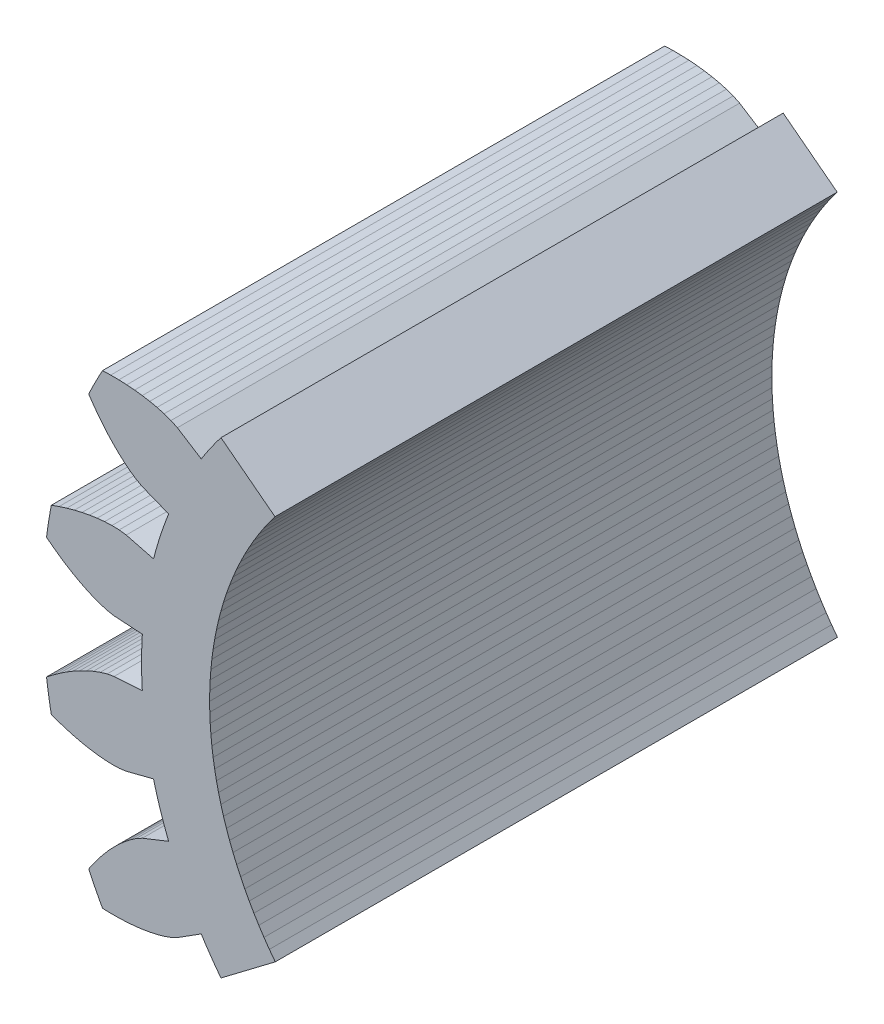
SolidWorks part; units mm, degrees
ref_plane "Alzado" through (0, 0, 0) normal (0, 0, 1) x (1, 0, 0)
ref_plane "Planta" through (0, 0, 0) normal (0, 1, 0) x (1, 0, 0)
ref_plane "Vista lateral" through (0, 0, 0) normal (1, 0, 0) x (0, 0, -1)
sketch "Croquis1" plane through (0, 0, 0) normal (0, 0, 1) x (1, 0, 0)
  line L0 (-17.3546, 13.3167) -> (-17.524, 13.0929)
  line L1 (-17.524, 13.0929) -> (-17.6906, 12.867)
  line L2 (-17.6906, 12.867) -> (-17.8542, 12.6389)
  line L3 (-17.8542, 12.6389) -> (-18.0149, 12.4088)
  line L4 (-18.0149, 12.4088) -> (-18.1726, 12.1767)
  line L5 (-18.1726, 12.1767) -> (-18.3274, 11.9425)
  line L6 (-18.3274, 11.9425) -> (-18.4791, 11.7064)
  line L7 (-18.4791, 11.7064) -> (-18.8185, 11.9214)
  line L8 (-18.8185, 11.9214) -> (-19.1579, 12.1364)
  line L9 (-19.1579, 12.1364) -> (-19.4973, 12.3514)
  line L10 (-19.4973, 12.3514) -> (-19.8367, 12.5664)
  line L11 (-19.8367, 12.5664) -> (-20.2018, 12.7408)
  line L12 (-20.2018, 12.7408) -> (-20.5901, 12.878)
  line L13 (-20.5901, 12.878) -> (-20.9936, 12.9901)
  line L14 (-20.9936, 12.9901) -> (-21.4094, 13.0809)
  line L15 (-21.4094, 13.0809) -> (-21.8359, 13.1525)
  line L16 (-21.8359, 13.1525) -> (-22.272, 13.2059)
  line L17 (-22.272, 13.2059) -> (-22.7168, 13.2422)
  line L18 (-22.7168, 13.2422) -> (-23.1695, 13.2617)
  line L19 (-23.1695, 13.2617) -> (-23.6295, 13.265)
  line L20 (-23.6295, 13.265) -> (-24.0962, 13.2523)
  line L21 (-24.0962, 13.2523) -> (-24.2617, 12.9468)
  line L22 (-24.2617, 12.9468) -> (-24.4233, 12.6393)
  line L23 (-24.4233, 12.6393) -> (-24.5811, 12.3297)
  line L24 (-24.5811, 12.3297) -> (-24.7349, 12.0182)
  line L25 (-24.7349, 12.0182) -> (-24.8847, 11.7047)
  line L26 (-24.8847, 11.7047) -> (-24.6207, 11.3197)
  line L27 (-24.6207, 11.3197) -> (-24.3477, 10.9495)
  line L28 (-24.3477, 10.9495) -> (-24.0657, 10.5947)
  line L29 (-24.0657, 10.5947) -> (-23.775, 10.2562)
  line L30 (-23.775, 10.2562) -> (-23.4754, 9.9348)
  line L31 (-23.4754, 9.9348) -> (-23.1668, 9.6318)
  line L32 (-23.1668, 9.6318) -> (-22.8489, 9.3488)
  line L33 (-22.8489, 9.3488) -> (-22.5211, 9.0883)
  line L34 (-22.5211, 9.0883) -> (-22.1819, 8.8548)
  line L35 (-22.1819, 8.8548) -> (-21.8262, 8.6619)
  line L36 (-21.8262, 8.6619) -> (-21.4527, 8.5137)
  line L37 (-21.4527, 8.5137) -> (-21.0793, 8.3655)
  line L38 (-21.0793, 8.3655) -> (-20.7058, 8.2173)
  line L39 (-20.7058, 8.2173) -> (-20.3324, 8.0691)
  line L40 (-20.3324, 8.0691) -> (-20.4757, 7.6981)
  line L41 (-20.4757, 7.6981) -> (-20.6123, 7.3245)
  line L42 (-20.6123, 7.3245) -> (-20.7421, 6.9486)
  line L43 (-20.7421, 6.9486) -> (-20.865, 6.5703)
  line L44 (-20.865, 6.5703) -> (-20.981, 6.1899)
  line L45 (-20.981, 6.1899) -> (-21.09, 5.8075)
  line L46 (-21.09, 5.8075) -> (-21.1921, 5.4231)
  line L47 (-21.1921, 5.4231) -> (-21.5814, 5.5227)
  line L48 (-21.5814, 5.5227) -> (-21.9706, 5.6223)
  line L49 (-21.9706, 5.6223) -> (-22.3599, 5.7219)
  line L50 (-22.3599, 5.7219) -> (-22.7491, 5.8215)
  line L51 (-22.7491, 5.8215) -> (-23.1502, 5.8745)
  line L52 (-23.1502, 5.8745) -> (-23.5619, 5.885)
  line L53 (-23.5619, 5.885) -> (-23.9802, 5.8669)
  line L54 (-23.9802, 5.8669) -> (-24.4038, 5.8248)
  line L55 (-24.4038, 5.8248) -> (-24.8315, 5.7611)
  line L56 (-24.8315, 5.7611) -> (-25.2628, 5.6772)
  line L57 (-25.2628, 5.6772) -> (-25.697, 5.5742)
  line L58 (-25.697, 5.5742) -> (-26.1336, 5.4529)
  line L59 (-26.1336, 5.4529) -> (-26.5721, 5.3139)
  line L60 (-26.5721, 5.3139) -> (-27.012, 5.1576)
  line L61 (-27.012, 5.1576) -> (-27.075, 4.8159)
  line L62 (-27.075, 4.8159) -> (-27.1337, 4.4734)
  line L63 (-27.1337, 4.4734) -> (-27.1881, 4.1303)
  line L64 (-27.1881, 4.1303) -> (-27.2381, 3.7865)
  line L65 (-27.2381, 3.7865) -> (-27.2837, 3.442)
  line L66 (-27.2837, 3.442) -> (-26.9136, 3.1574)
  line L67 (-26.9136, 3.1574) -> (-26.5396, 2.8897)
  line L68 (-26.5396, 2.8897) -> (-26.1618, 2.6395)
  line L69 (-26.1618, 2.6395) -> (-25.7807, 2.4073)
  line L70 (-25.7807, 2.4073) -> (-25.3965, 2.1943)
  line L71 (-25.3965, 2.1943) -> (-25.0093, 2.0014)
  line L72 (-25.0093, 2.0014) -> (-24.6195, 1.8305)
  line L73 (-24.6195, 1.8305) -> (-24.2273, 1.6841)
  line L74 (-24.2273, 1.6841) -> (-23.8325, 1.5668)
  line L75 (-23.8325, 1.5668) -> (-23.4346, 1.4933)
  line L76 (-23.4346, 1.4933) -> (-23.0336, 1.4677)
  line L77 (-23.0336, 1.4677) -> (-22.6327, 1.4422)
  line L78 (-22.6327, 1.4422) -> (-22.2317, 1.4166)
  line L79 (-22.2317, 1.4166) -> (-21.8307, 1.3911)
  line L80 (-21.8307, 1.3911) -> (-21.8524, 0.994)
  line L81 (-21.8524, 0.994) -> (-21.8669, 0.5965)
  line L82 (-21.8669, 0.5965) -> (-21.8741, 0.1989)
  line L83 (-21.8741, 0.1989) -> (-21.8741, -0.1989)
  line L84 (-21.8741, -0.1989) -> (-21.8669, -0.5965)
  line L85 (-21.8669, -0.5965) -> (-21.8524, -0.994)
  line L86 (-21.8524, -0.994) -> (-21.8307, -1.3911)
  line L87 (-21.8307, -1.3911) -> (-22.2317, -1.4166)
  line L88 (-22.2317, -1.4166) -> (-22.6327, -1.4422)
  line L89 (-22.6327, -1.4422) -> (-23.0336, -1.4677)
  line L90 (-23.0336, -1.4677) -> (-23.4346, -1.4933)
  line L91 (-23.4346, -1.4933) -> (-23.8325, -1.5668)
  line L92 (-23.8325, -1.5668) -> (-24.2273, -1.6841)
  line L93 (-24.2273, -1.6841) -> (-24.6195, -1.8305)
  line L94 (-24.6195, -1.8305) -> (-25.0093, -2.0014)
  line L95 (-25.0093, -2.0014) -> (-25.3965, -2.1943)
  line L96 (-25.3965, -2.1943) -> (-25.7807, -2.4073)
  line L97 (-25.7807, -2.4073) -> (-26.1618, -2.6395)
  line L98 (-26.1618, -2.6395) -> (-26.5396, -2.8897)
  line L99 (-26.5396, -2.8897) -> (-26.9136, -3.1574)
  line L100 (-26.9136, -3.1574) -> (-27.2837, -3.442)
  line L101 (-27.2837, -3.442) -> (-27.2381, -3.7865)
  line L102 (-27.2381, -3.7865) -> (-27.1881, -4.1303)
  line L103 (-27.1881, -4.1303) -> (-27.1337, -4.4734)
  line L104 (-27.1337, -4.4734) -> (-27.075, -4.8159)
  line L105 (-27.075, -4.8159) -> (-27.012, -5.1576)
  line L106 (-27.012, -5.1576) -> (-26.5721, -5.3139)
  line L107 (-26.5721, -5.3139) -> (-26.1336, -5.4529)
  line L108 (-26.1336, -5.4529) -> (-25.697, -5.5742)
  line L109 (-25.697, -5.5742) -> (-25.2628, -5.6772)
  line L110 (-25.2628, -5.6772) -> (-24.8315, -5.7611)
  line L111 (-24.8315, -5.7611) -> (-24.4038, -5.8248)
  line L112 (-24.4038, -5.8248) -> (-23.9802, -5.8669)
  line L113 (-23.9802, -5.8669) -> (-23.5619, -5.885)
  line L114 (-23.5619, -5.885) -> (-23.1502, -5.8745)
  line L115 (-23.1502, -5.8745) -> (-22.7491, -5.8215)
  line L116 (-22.7491, -5.8215) -> (-22.3599, -5.7219)
  line L117 (-22.3599, -5.7219) -> (-21.9706, -5.6223)
  line L118 (-21.9706, -5.6223) -> (-21.5814, -5.5227)
  line L119 (-21.5814, -5.5227) -> (-21.1921, -5.4231)
  line L120 (-21.1921, -5.4231) -> (-21.09, -5.8075)
  line L121 (-21.09, -5.8075) -> (-20.981, -6.1899)
  line L122 (-20.981, -6.1899) -> (-20.865, -6.5703)
  line L123 (-20.865, -6.5703) -> (-20.7421, -6.9486)
  line L124 (-20.7421, -6.9486) -> (-20.6123, -7.3245)
  line L125 (-20.6123, -7.3245) -> (-20.4757, -7.6981)
  line L126 (-20.4757, -7.6981) -> (-20.3324, -8.0691)
  line L127 (-20.3324, -8.0691) -> (-20.7058, -8.2173)
  line L128 (-20.7058, -8.2173) -> (-21.0793, -8.3655)
  line L129 (-21.0793, -8.3655) -> (-21.4527, -8.5137)
  line L130 (-21.4527, -8.5137) -> (-21.8262, -8.6619)
  line L131 (-21.8262, -8.6619) -> (-22.1819, -8.8548)
  line L132 (-22.1819, -8.8548) -> (-22.5211, -9.0883)
  line L133 (-22.5211, -9.0883) -> (-22.8489, -9.3488)
  line L134 (-22.8489, -9.3488) -> (-23.1668, -9.6318)
  line L135 (-23.1668, -9.6318) -> (-23.4754, -9.9348)
  line L136 (-23.4754, -9.9348) -> (-23.775, -10.2562)
  line L137 (-23.775, -10.2562) -> (-24.0657, -10.5947)
  line L138 (-24.0657, -10.5947) -> (-24.3477, -10.9495)
  line L139 (-24.3477, -10.9495) -> (-24.6207, -11.3197)
  line L140 (-24.6207, -11.3197) -> (-24.8847, -11.7047)
  line L141 (-24.8847, -11.7047) -> (-24.7349, -12.0182)
  line L142 (-24.7349, -12.0182) -> (-24.5811, -12.3297)
  line L143 (-24.5811, -12.3297) -> (-24.4233, -12.6393)
  line L144 (-24.4233, -12.6393) -> (-24.2617, -12.9468)
  line L145 (-24.2617, -12.9468) -> (-24.0962, -13.2523)
  line L146 (-24.0962, -13.2523) -> (-23.6295, -13.265)
  line L147 (-23.6295, -13.265) -> (-23.1695, -13.2617)
  line L148 (-23.1695, -13.2617) -> (-22.7168, -13.2422)
  line L149 (-22.7168, -13.2422) -> (-22.272, -13.2059)
  line L150 (-22.272, -13.2059) -> (-21.8359, -13.1525)
  line L151 (-21.8359, -13.1525) -> (-21.4094, -13.0809)
  line L152 (-21.4094, -13.0809) -> (-20.9936, -12.9901)
  line L153 (-20.9936, -12.9901) -> (-20.5901, -12.878)
  line L154 (-20.5901, -12.878) -> (-20.2018, -12.7408)
  line L155 (-20.2018, -12.7408) -> (-19.8367, -12.5664)
  line L156 (-19.8367, -12.5664) -> (-19.4973, -12.3514)
  line L157 (-19.4973, -12.3514) -> (-19.1579, -12.1364)
  line L158 (-19.1579, -12.1364) -> (-18.8185, -11.9214)
  line L159 (-18.8185, -11.9214) -> (-18.4791, -11.7064)
  line L160 (-18.4791, -11.7064) -> (-18.3274, -11.9425)
  line L161 (-18.3274, -11.9425) -> (-18.1726, -12.1767)
  line L162 (-18.1726, -12.1767) -> (-18.0149, -12.4088)
  line L163 (-18.0149, -12.4088) -> (-17.8542, -12.6389)
  line L164 (-17.8542, -12.6389) -> (-17.6906, -12.867)
  line L165 (-17.6906, -12.867) -> (-17.524, -13.0929)
  line L166 (-17.524, -13.0929) -> (-17.3546, -13.3167)
  line L167 (-17.3546, -13.3167) -> (-14.2654, -10.9775)
  line L168 (-14.2654, -10.9775) -> (-14.6, -10.5281)
  line L169 (-14.6, -10.5281) -> (-14.9067, -10.0891)
  line L170 (-14.9067, -10.0891) -> (-15.2002, -9.6413)
  line L171 (-15.2002, -9.6413) -> (-15.4803, -9.1849)
  line L172 (-15.4803, -9.1849) -> (-15.7466, -8.7203)
  line L173 (-15.7466, -8.7203) -> (-15.999, -8.2481)
  line L174 (-15.999, -8.2481) -> (-16.2373, -7.7685)
  line L175 (-16.2373, -7.7685) -> (-16.4612, -7.2821)
  line L176 (-16.4612, -7.2821) -> (-16.6705, -6.7892)
  line L177 (-16.6705, -6.7892) -> (-16.8651, -6.2904)
  line L178 (-16.8651, -6.2904) -> (-17.0447, -5.7859)
  line L179 (-17.0447, -5.7859) -> (-17.2093, -5.2763)
  line L180 (-17.2093, -5.2763) -> (-17.3586, -4.7621)
  line L181 (-17.3586, -4.7621) -> (-17.4926, -4.2437)
  line L182 (-17.4926, -4.2437) -> (-17.6111, -3.7215)
  line L183 (-17.6111, -3.7215) -> (-17.714, -3.196)
  line L184 (-17.714, -3.196) -> (-17.8012, -2.6676)
  line L185 (-17.8012, -2.6676) -> (-17.8727, -2.1369)
  line L186 (-17.8727, -2.1369) -> (-17.9284, -1.6044)
  line L187 (-17.9284, -1.6044) -> (-17.9681, -1.0704)
  line L188 (-17.9681, -1.0704) -> (-17.992, -0.5354)
  line L189 (-17.992, -0.5354) -> (-18, 0)
  line L190 (-18, 0) -> (-17.992, 0.5354)
  line L191 (-17.992, 0.5354) -> (-17.9681, 1.0704)
  line L192 (-17.9681, 1.0704) -> (-17.9284, 1.6044)
  line L193 (-17.9284, 1.6044) -> (-17.8727, 2.1369)
  line L194 (-17.8727, 2.1369) -> (-17.8012, 2.6676)
  line L195 (-17.8012, 2.6676) -> (-17.714, 3.196)
  line L196 (-17.714, 3.196) -> (-17.6111, 3.7215)
  line L197 (-17.6111, 3.7215) -> (-17.4926, 4.2437)
  line L198 (-17.4926, 4.2437) -> (-17.3586, 4.7621)
  line L199 (-17.3586, 4.7621) -> (-17.2093, 5.2763)
  line L200 (-17.2093, 5.2763) -> (-17.0447, 5.7859)
  line L201 (-17.0447, 5.7859) -> (-16.8651, 6.2904)
  line L202 (-16.8651, 6.2904) -> (-16.6705, 6.7892)
  line L203 (-16.6705, 6.7892) -> (-16.4612, 7.2821)
  line L204 (-16.4612, 7.2821) -> (-16.2373, 7.7685)
  line L205 (-16.2373, 7.7685) -> (-15.999, 8.2481)
  line L206 (-15.999, 8.2481) -> (-15.7466, 8.7203)
  line L207 (-15.7466, 8.7203) -> (-15.4803, 9.1849)
  line L208 (-15.4803, 9.1849) -> (-15.2002, 9.6413)
  line L209 (-15.2002, 9.6413) -> (-14.9067, 10.0891)
  line L210 (-14.9067, 10.0891) -> (-14.6, 10.5281)
  line L211 (-14.6, 10.5281) -> (-14.2804, 10.9577)
  line L212 (-14.2804, 10.9577) -> (-17.3546, 13.3167)
extrude "Saliente-Extruir1" add sketch "Croquis1" along normal blind 16 and the other way blind 16
